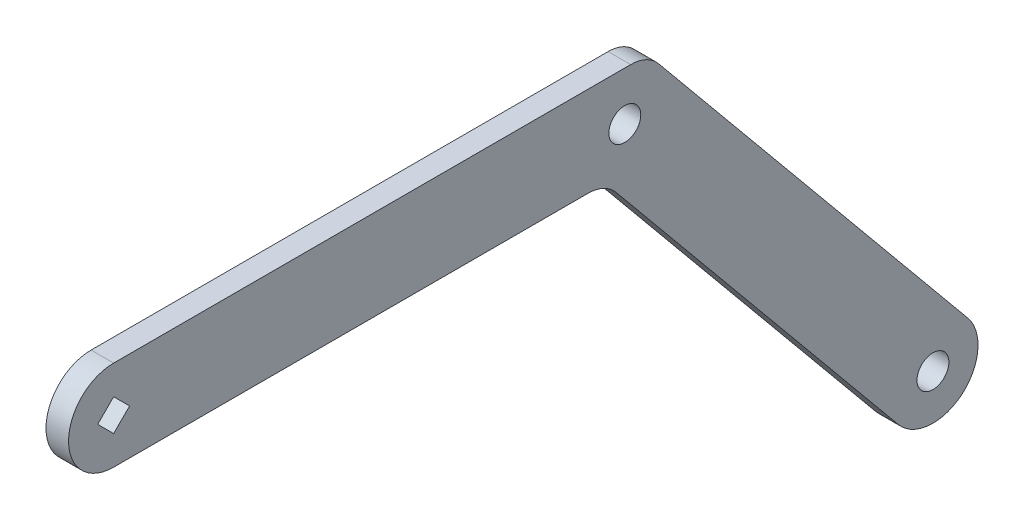
SolidWorks part; units mm, degrees
material "Custom Plastic"
ref_plane "Front Plane" through (0, 0, 0) normal (0, 0, 1) x (1, 0, 0)
ref_plane "Top Plane" through (0, 0, 0) normal (0, 1, 0) x (1, 0, 0)
ref_plane "Right Plane" through (0, 0, 0) normal (1, 0, 0) x (0, 0, -1)
sketch "Sketch1" plane through (0, 0, 0) normal (1, 0, 0) x (0, 0, -1)
  line L0 (115.3711, -52.3257) -> (0, 0) construction
  line L1 (0, 0) -> (72.2086, 0) construction
  line L2 (0, 2.2451) -> (2.2451, 0)
  line L3 (0, 2.2451) -> (-2.2451, 0)
  line L4 (-2.2451, 0) -> (0, -2.2451)
  line L5 (2.2451, 0) -> (0, -2.2451)
  line L6 (0, 2.2451) -> (0, -2.2451) construction
  line L7 (-2.2451, 0) -> (2.2451, 0) construction
  line L8 (117.6161, -52.3257) -> (115.3711, -54.5707) construction
  line L9 (117.6161, -52.3257) -> (115.3711, -50.0806) construction
  line L10 (115.3711, -50.0806) -> (113.126, -52.3257) construction
  line L11 (115.3711, -54.5707) -> (113.126, -52.3257) construction
  line L12 (117.6161, -52.3257) -> (113.126, -52.3257) construction
  line L13 (115.3711, -50.0806) -> (115.3711, -54.5707) construction
  line L14 (72.2086, 0) -> (115.3711, -52.3257) construction
  line L15 (0, -6.35) -> (69.215, -6.35)
  line L16 (75.2022, 6.35) -> (120.2696, -48.285)
  line L17 (120.2696, -48.285) -> (110.4725, -56.3664) construction
  line L18 (69.215, -6.35) -> (110.4725, -56.3664)
  line L19 (75.2022, 6.35) -> (0, 6.35)
  line L20 (0, -6.35) -> (0, 6.35) construction
  line L21 (72.2086, 0) -> (75.2022, 6.35) construction
  circle A0 centre (115.3711, -52.3257) radius 2.2451
  arc A1 (0, 6.35) -> (0, -6.35) centre (0, 0) ccw
  arc A2 (120.2696, -48.285) -> (110.4725, -56.3664) centre (115.3711, -52.3257) cw
  dimension "D1" = 126.6825
  dimension "D2" = 3.175
  dimension "D3" = 69.215
  dimension "D4" = 6.35
extrude "Boss-Extrude1" add sketch "Sketch1" along normal blind 3.175
fillet "Fillet1" radius 5.08 2 edges at (1.5875, 6.35, -75.2022) (1.5875, -6.35, -69.215)
sketch "Sketch2" plane through (3.175, 0, 0) normal (1, 0, 0) x (0, 0, -1)
  line L0 (68.9863, -6.835) -> (71.9799, -0.485) construction
  line L1 (71.9799, -0.485) -> (74.9735, 5.865) construction
  circle A0 centre (71.9799, -0.485) radius 2.2479
  arc A1 (70.7389, -8.1975) -> (66.8201, -6.35) centre (66.8201, -11.43) ccw construction
  arc A2 (76.7261, 4.5025) -> (72.8073, 6.35) centre (72.8073, 1.27) ccw construction
  dimension "D1" = 4.4958
extrude "Torque prevention" cut sketch "Sketch2" against normal through all
